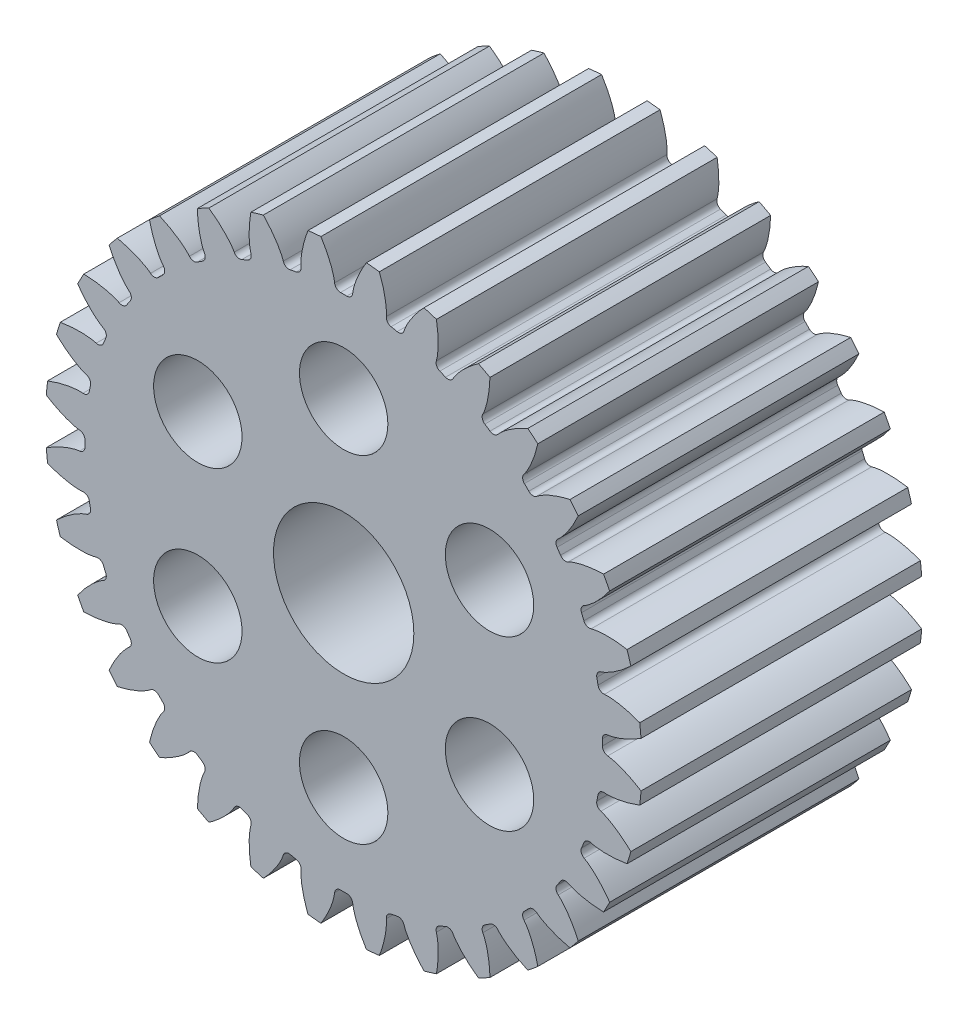
SolidWorks part; units mm, degrees
material "Plain Carbon Steel"
ref_plane "Front Plane" through (0, 0, 0) normal (0, 0, 1) x (1, 0, 0)
ref_plane "Top Plane" through (0, 0, 0) normal (0, 1, 0) x (1, 0, 0)
ref_plane "Right Plane" through (0, 0, 0) normal (1, 0, 0) x (0, 0, -1)
sketch "Sketch1" plane through (0, 0, 0) normal (0, 0, 1) x (1, 0, 0)
  line L0 (0, 0) -> (0, 12.7) construction
  line L1 (-4.0817, 14.1856) -> (4.0817, 11.2144) construction
  circle A0 centre (0, 0) radius 11.7078 construction
  circle A1 centre (0, 0) radius 13.4938 construction
  circle A2 centre (0, 0) radius 12.7 construction
  circle A3 centre (0, 0) radius 11.9341 construction
  point P8 (406.4, 0)
  point P13 (406.4, 0)
  dimension "OD | Outside Diameter" = 26.9875
  dimension "Root Diameter" = 23.4156
  dimension "Gear Pitch Diameter" = 25.4
  dimension "Base Diameter" = 23.8682
  dimension "Pressure Angle" = 20
  dimension "Number of Teeth" = 812.8
  dimension "Gear Pitch | Diametral Pitch" = 812.8
sketch "Sketch2" plane through (0, 0, 0) normal (1, 0, 0) x (0, 0, -1)
  line L0 (-6.35, 0) -> (6.35, 0) construction
  point P2 (7.1437, 0)
  point P5 (13.8906, 0)
  point P6 (-7.1437, 0)
  dimension "Length" = 12.7
  dimension "D1" = 13.4937
  dimension "D2" = 20.2406
  dimension "D3" = 13.4937
sketch "Sketch3" plane through (0, 0, 0) normal (0, 0, 1) x (1, 0, 0)
  circle A0 centre (0, 0) radius 13.4938
  circle A1 centre (0, 0) radius 13.4937 construction
extrude "Boss-Extrude1" add sketch "Sketch3" against normal up to vertex (6.35 mm away) and the other way up to vertex (6.35 mm away) up to point (0, 0, -6.35) other way up to point (0, 0, 6.35)
sketch "Sketch4" plane through (0, 0, 0) normal (0, 0, 1) x (1, 0, 0)
  line L0 (0, 0) -> (11.701, 0.4001) construction
  line L2 (0, 0) -> (11.701, -0.4001) construction
  line L4 (11.701, 0.4001) -> (11.9271, 0.4079)
  line L5 (11.9271, -0.4079) -> (11.701, -0.4001)
  arc A0 (11.701, 0.4001) -> (11.701, -0.4001) centre (0, 0) cw
  arc A3 (13.4545, 1.0288) -> (13.4545, -1.0288) centre (0, 0) cw
  circle A4 centre (0, 0) radius 13.4937 construction
  spline S0 degree 4 poles (11.9271, 0.4079) (11.9296, 0.408) (11.9365, 0.4084) (11.9495, 0.4095) (11.9706, 0.4117) (11.9976, 0.4153) (12.0324, 0.4207) (12.0733, 0.4281) (12.1181, 0.4373) (12.1668, 0.4485) (12.2153, 0.4607) (12.2636, 0.4738) (12.3116, 0.4878) (12.3697, 0.5057) (12.4391, 0.5286) (12.52, 0.5574) (12.6114, 0.5926) (12.7042, 0.631) (12.7953, 0.6709) (12.8869, 0.7137) (12.9752, 0.7568) (13.0666, 0.8041) (13.1507, 0.8491) (13.2444, 0.9022) (13.3199, 0.9459) (13.419, 1.0064) (13.4774, 1.0431) (13.5454, 1.087) (13.5756, 1.107) (13.5941, 1.1193) knots 0 0 0 0 0 0.005377 0.015084 0.028532 0.04661 0.064855 0.092111 0.119476 0.146842 0.174209 0.201575 0.228941 0.256307 0.307035 0.361767 0.4165 0.471232 0.525964 0.580697 0.635429 0.690161 0.744894 0.799626 0.854358 0.909091 0.954545 1 1 1 1 1 construction
  spline S1 degree 4 poles (11.9271, 0.4079) (11.9296, 0.408) (11.9365, 0.4084) (11.9495, 0.4095) (11.9706, 0.4117) (11.9976, 0.4153) (12.0324, 0.4207) (12.0733, 0.4281) (12.1181, 0.4373) (12.1668, 0.4485) (12.2153, 0.4607) (12.2636, 0.4738) (12.3116, 0.4878) (12.3697, 0.5057) (12.4391, 0.5286) (12.52, 0.5574) (12.6114, 0.5926) (12.7042, 0.631) (12.7953, 0.6709) (12.8869, 0.7137) (12.9752, 0.7568) (13.0666, 0.8041) (13.1507, 0.8491) (13.2444, 0.9022) (13.3199, 0.9459) (13.3975, 0.9933) (13.4352, 1.0167) (13.4545, 1.0288) knots 0 0 0 0 0 0.005377 0.015084 0.028532 0.04661 0.064855 0.092111 0.119476 0.146842 0.174209 0.201575 0.228941 0.256307 0.307035 0.361767 0.4165 0.471232 0.525964 0.580697 0.635429 0.690161 0.744894 0.799626 0.854358 0.909091 0.909091 0.909091 0.909091 0.909091
  spline S2 degree 4 poles (11.9271, -0.4079) (11.9296, -0.408) (11.9365, -0.4084) (11.9495, -0.4095) (11.9706, -0.4117) (11.9976, -0.4153) (12.0324, -0.4207) (12.0733, -0.4281) (12.1181, -0.4373) (12.1668, -0.4485) (12.2153, -0.4607) (12.2636, -0.4738) (12.3116, -0.4878) (12.3697, -0.5057) (12.4391, -0.5286) (12.52, -0.5574) (12.6114, -0.5926) (12.7042, -0.631) (12.7953, -0.6709) (12.8869, -0.7137) (12.9752, -0.7568) (13.0666, -0.8041) (13.1507, -0.8491) (13.2444, -0.9022) (13.3199, -0.9459) (13.419, -1.0064) (13.4774, -1.0431) (13.5454, -1.087) (13.5756, -1.107) (13.5941, -1.1193) knots 0 0 0 0 0 0.005377 0.015084 0.028532 0.04661 0.064855 0.092111 0.119476 0.146842 0.174209 0.201575 0.228941 0.256307 0.307035 0.361767 0.4165 0.471232 0.525964 0.580697 0.635429 0.690161 0.744894 0.799626 0.854358 0.909091 0.954545 1 1 1 1 1 construction
  spline S3 degree 4 poles (11.9271, -0.4079) (11.9296, -0.408) (11.9365, -0.4084) (11.9495, -0.4095) (11.9706, -0.4117) (11.9976, -0.4153) (12.0324, -0.4207) (12.0733, -0.4281) (12.1181, -0.4373) (12.1668, -0.4485) (12.2153, -0.4607) (12.2636, -0.4738) (12.3116, -0.4878) (12.3697, -0.5057) (12.4391, -0.5286) (12.52, -0.5574) (12.6114, -0.5926) (12.7042, -0.631) (12.7953, -0.6709) (12.8869, -0.7137) (12.9752, -0.7568) (13.0666, -0.8041) (13.1507, -0.8491) (13.2444, -0.9022) (13.3199, -0.9459) (13.3975, -0.9933) (13.4352, -1.0167) (13.4545, -1.0288) knots 0 0 0 0 0 0.005377 0.015084 0.028532 0.04661 0.064855 0.092111 0.119476 0.146842 0.174209 0.201575 0.228941 0.256307 0.307035 0.361767 0.4165 0.471232 0.525964 0.580697 0.635429 0.690161 0.744894 0.799626 0.854358 0.909091 0.909091 0.909091 0.909091 0.909091
  dimension "D1" = 23.4156
extrude "Cut-Extrude1" cut sketch "Sketch4" against normal through all both and the other way through all
fillet "Fillet1" radius 0.2663 2 edges at (11.701, -0.4001, 0) (11.701, 0.4001, 0)
pattern_circular "CirPattern1" count 32 over 360 about axis through (0, 0, 6.35) along (0, 0, -1) of "Cut-Extrude1", "Fillet1"
sketch "Sketch5" plane through (0, 0, 6.35) normal (0, 0, 1) x (1, 0, 0)
  point P0 (0, 0)
hole_wizard "1/4 (0.2500) Dowel Hole1" positions "Sketch5" profile "Sketch6" hole size "1/4" standard "ANSI Inch" end condition through all
sketch "Sketch6" plane through (0, 0, 6.35) normal (1, 0, 0) x (0, -1, 0)
  line L0 (0, 0) -> (0, 12.7)
  line L1 (0, 12.7) -> (3.175, 12.7)
  line L2 (3.175, 12.7) -> (3.175, 0)
  line L5 (3.175, 0) -> (0, 0)
  line L11 (0, -6.35) -> (0, 107.95) construction
  dimension "Thru Hole Dia." = 6.35
  dimension "Thru Hole Depth" = 12.7
sketch "Sketch7" plane through (0, 0, 6.35) normal (0, 0, 1) x (1, 0, 0)
  point P0 (0, 0)
  point P1 (0, 7.62)
  dimension "D1" = 7.62
ref_axis "Axis1" through (0, 0, -6.35) along (0, 0, 1)
hole_wizard "Ø4.0mm Dowel Hole1" positions "Sketch7" profile "Sketch8" hole size "Ø4.0" standard "ANSI Metric" end condition through all
sketch "Sketch8" plane through (0, 0, 6.35) normal (1, 0, 0) x (0, -1, 0)
  line L0 (0, 0) -> (0, 12.7)
  line L1 (0, 12.7) -> (2, 12.7)
  line L2 (2, 12.7) -> (2, 0)
  line L5 (2, 0) -> (0, 0)
  line L11 (0, -6.35) -> (0, 107.95) construction
  dimension "Thru Hole Dia." = 4
  dimension "Thru Hole Depth" = 12.7
pattern_circular "CirPattern2" count 6 over 360 about axis through (0, 0, 6.35) along (0, 0, 1) of "Ø4.0mm Dowel Hole1"
equation "\"Root Diameter@Sketch1\"=\"Root Diameter\""
equation "\"OD | Outside Diameter@Sketch1\"=\"Outside Diameter\""
equation "\"D1@CirPattern1\"=\"Number of Teeth\""
equation "\"Diametral Pitch\"=32"
equation "\"Number of Teeth\"= 32"
equation "\"Pressure Angle\"=20"
equation "\"Pitch Diameter\"= \"Number of Teeth\" / \"Diametral Pitch\""
equation "\"Base Diameter\"= \"Pitch Diameter\" * cos ( \"Pressure Angle\" )"
equation "\"Outside Diameter\"= ( \"Number of Teeth\" + 2 ) / \"Diametral Pitch\""
equation "\"Dedendum\"= 1.25 / \"Diametral Pitch\""
equation "\"Root Diameter\"= \"Pitch Diameter\" - ( 2 * \"Dedendum\" )"
equation "\"Pitch Angle\"= 360deg / \"Number of Teeth\""
equation "\"Alpha\"= sqr ( \"Pitch Diameter\" ^ 2 - \"Base Diameter\" ^ 2 ) / \"Base Diameter\" * 180 / PI - \"Pressure Angle\""
equation "\"Beta\"= ( \"Pitch Angle\" / 4 - \"Alpha\" )"
equation "\"Phi\"= sqr ( ( \"Outside Diameter\" / 2 ) ^ 2 - ( \"Base Diameter\" / 2 ) ^ 2 ) / ( \"Base Diameter\" / 2 )"
equation "\"Addendum\"= 1 / \"Diametral Pitch\""
equation "\"WorkingDepth\"= 2 / \"Diametral Pitch\""
equation "\"WholeDepth\"= 2.25 / \"Diametral Pitch\""
equation "\"Clearance\"= 0.25 / \"Diametral Pitch\""
equation "\"ToothThickness\"= ( pi * 2 ) / \"Diametral Pitch\""
equation "\"CircularPitch\"= pi / \"Diametral Pitch\""
equation "\"Number of Teeth@Sketch1\"=\"Number of Teeth\""
equation "\"Gear Pitch | Diametral Pitch@Sketch1\"=\"Diametral Pitch\""
equation "\"Pressure Angle@Sketch1\"=\"Pressure Angle\""
equation "\"Gear Pitch Diameter@Sketch1\"=\"Pitch Diameter\""
equation "\"Base Diameter@Sketch1\"=\"Base Diameter\""
equation "\"Fillet\"= \"Clearance\" * cos ( \"Pressure Angle\" ) * tan ( ( 90 + \"Pressure Angle\" ) / 2 )"
equation "\"D1@Fillet1\"=\"Fillet\""
equation "\"D1@Sketch4\"=if( \"Base Diameter\">\"Root Diameter\",\"Root Diameter\",\"Base Diameter\"-.00001)"
equation "\"D1@Sketch2\"=\"OD | Outside Diameter@Sketch1\"*2*0.5*0.5"
equation "\"D2@Sketch2\"=\"D1@Sketch2\"*1.5"
equation "\"D3@Sketch2\"=\"D1@Sketch2\""
equation "\"Length\"= .5in"
equation "\"Length@Sketch2\"= \"Length\""
